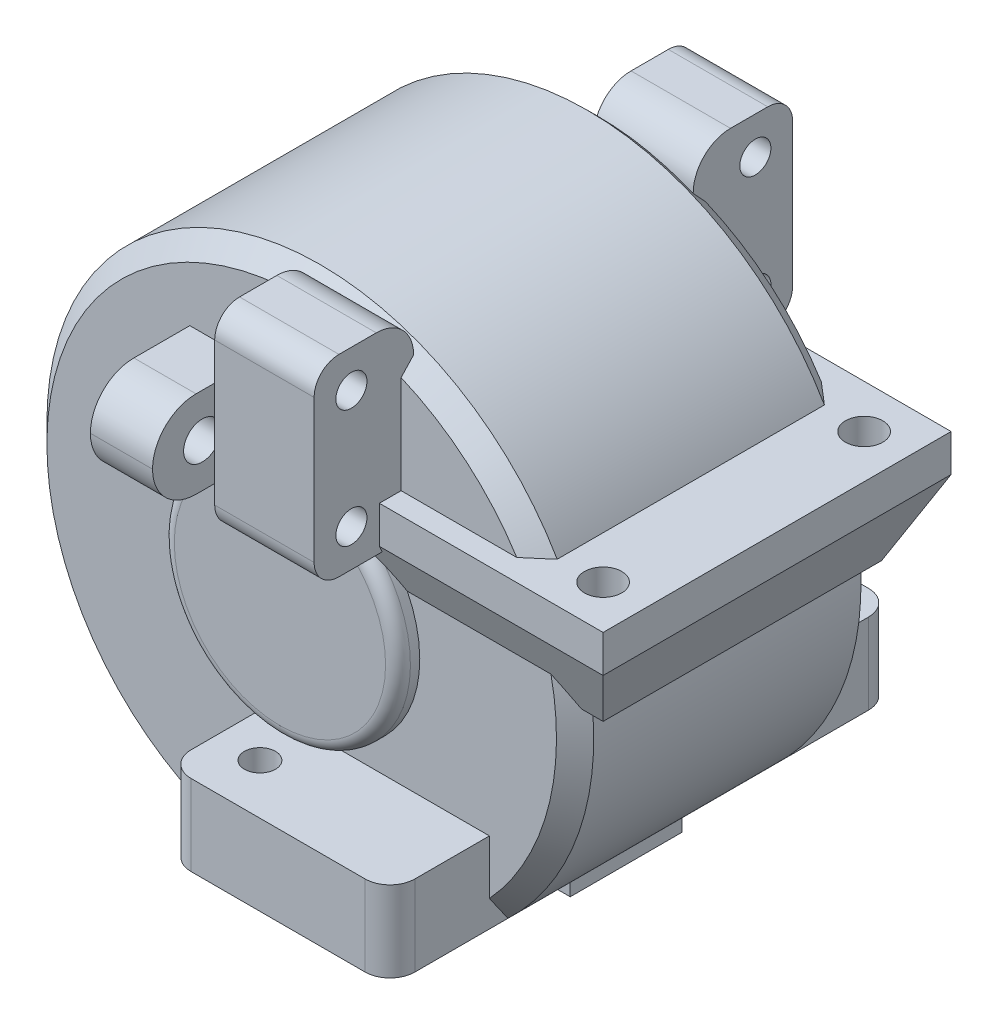
SolidWorks part; units mm, degrees
ref_plane "Front Plane" through (0, 0, 0) normal (0, 0, 1) x (1, 0, 0)
ref_plane "Top Plane" through (0, 0, 0) normal (0, 1, 0) x (1, 0, 0)
ref_plane "Right Plane" through (0, 0, 0) normal (1, 0, 0) x (0, 0, -1)
sketch "Sketch2" plane through (0, 0, 0) normal (0, 0, 1) x (1, 0, 0)
  circle A0 centre (0, 0) radius 22
  circle A1 centre (0, 0) radius 9.5
  dimension "D1" = 44
  dimension "D2" = 19
extrude "Boss-Extrude1" add sketch "Sketch2" along normal blind 12.25 and the other way blind 12.25 contours A0
extrude "Boss-Extrude2" add sketch "Sketch2<3>" along normal blind 14 and the other way blind 14 contours A1
sketch "Sketch2<3>" plane through (0, 0, 0) normal (0, 0, 1) x (1, 0, 0) same geometry as "Sketch2"
chamfer "Chamfer1" distance 1.5 angle 45 2 edges at (22, 0, -12.25) (22, 0, 12.25)
fillet "Fillet1" radius 1 2 edges at (9.5, 0, -14) (9.5, 0, 14)
sketch "Sketch3" plane through (0, 0, -12.25) normal (0, 0, -1) x (-1, 0, 0)
  line L1 (-15.105, -9.505) -> (2.895, -9.505)
  line L2 (-15.105, -9.505) -> (-15.105, -15.995)
  line L3 (-15.105, -15.995) -> (2.895, -15.995)
  line L4 (2.895, -9.505) -> (2.895, -15.995)
  circle A0 centre (0, 0) radius 22 construction
  circle A1 centre (0, 0) radius 9.5 construction
  point P4 (0, 0)
  point P6 (0, 0)
  dimension "D3" = 9.505
  dimension "D1" = 18
  dimension "D2" = 6.49
extrude "Boss-Extrude7" add sketch "Sketch3" along normal blind 8 and the other way blind 2
sketch "Sketch4" plane through (0, -9.505, 0) normal (0, 1, 0) x (1, 0, 0)
  line L1 (-2.895, 20.25) -> (15.105, 20.25) construction
  circle A0 centre (-10.395, 16.2139) radius 1.25
  circle A1 centre (0.605, 16.2139) radius 1.25
  point P6 (6.105, 20.25)
  dimension "D1" = 2.5
  dimension "D2" = 2.5
  dimension "D3" = 11
  dimension "D4" = 5.5
extrude "Cut-Extrude1" cut sketch "Sketch4" against normal through all
fillet "Fillet2" radius 2 2 edges at (15.105, -12.75, -20.25) (-2.895, -12.75, -20.25)
ref_plane "Plane1" through (0, 1.995, 0) normal (0, 1, 0) x (1, 0, 0)
sketch "Sketch5" plane through (0, 1.995, 0) normal (0, 1, 0) x (1, 0, 0)
  line L1 (0, 14) -> (26, 14)
  line L2 (0, 14) -> (0, -14)
  line L3 (0, -14) -> (26, -14)
  line L4 (26, 14) -> (26, -14)
  point P4 (0, 0)
  dimension "D1" = 28
extrude "Boss-Extrude8" add sketch "Sketch5" along normal blind 9 contours L2 L1 L4 L3
chamfer "Chamfer2" distance 6 angle 25 3 edges at (17.1313, 1.995, 14) (26, 1.995, 0) (17.1313, 1.995, -14) first distance on face at (10.1747, 4.5108, 14) first distance on face at (26, 6.495, 0) first distance on face at (10.1747, 4.5108, -14)
sketch "Sketch6" plane through (0, 10.995, 0) normal (0, 1, 0) x (1, 0, 0)
  line L2 (26, 14) -> (26, -14) construction
  circle A0 centre (22.5, 10.5) radius 1.5
  circle A1 centre (22.5, -10.5) radius 1.5
  dimension "D1" = 10.5
  dimension "D2" = 3
  dimension "D3" = 3
  dimension "D4" = 3.5
  dimension "D5" = 3.5
  dimension "D6" = 21
extrude "Cut-Extrude2" cut sketch "Sketch6" against normal blind 6
sketch "Sketch7" plane through (0, 0, -12.25) normal (0, 0, -1) x (-1, 0, 0)
  line L0 (0, 10.995) -> (-26, 10.995) construction
  line L1 (0, 7.495) -> (-8, 7.495)
  line L2 (0, 7.495) -> (0, 22.995)
  line L3 (0, 22.995) -> (-8, 22.995)
  line L4 (-8, 7.495) -> (-8, 22.995)
  line L5 (-26, 10.995) -> (-26, 7.995) construction
  line L6 (4, 13.995) -> (9, 13.995)
  line L7 (4, 13.995) -> (4, 6.995)
  line L8 (4, 6.995) -> (9, 6.995)
  line L9 (9, 13.995) -> (9, 6.995)
  line M3 (0, 10.995) -> (0, 9.5)
  arc M6 (-20.0563, 4.2421) -> (-15.105, -13.8597) centre (0, 0) ccw
  line M7 (-17.302, 10.995) -> (0, 10.995)
  dimension "D1" = 15.5
  dimension "D2" = 8
  dimension "D3" = 12
  dimension "D4" = 7
  dimension "D5" = 5
  dimension "D6" = 35
  dimension "D7" = 9
  dimension "D8" = 18
extrude "Boss-Extrude11" add sketch "Sketch7" along normal blind 7 and the other way blind 1 contours L4 L2 M7 M6 | L4 L1 L2 M3 M7 | L4 L2 L3 M6 region at (4, 9.245, -12.25) region at (4, 16.995, -12.25)
extrude "Boss-Extrude13" add sketch "Sketch7<3>" along normal blind 8 contours L6 L9 L8 L7
sketch "Sketch7<3>" plane through (0, 0, -12.25) normal (0, 0, -1) x (-1, 0, 0) same geometry as "Sketch7"
sketch "Sketch10" plane through (8, 0, 0) normal (1, 0, 0) x (0, 0, -1)
  line L0 (19.25, 7.495) -> (19.25, 22.995) construction
  line L1 (19.25, 22.995) -> (11.25, 22.995) construction
  line L2 (19.25, 7.495) -> (13.7668, 7.495) construction
  circle A0 centre (16.25, 19.995) radius 1.25
  circle A1 centre (16.25, 10.495) radius 1.25
  point P8 (0, 0)
  point P10 (16.3117, 8.646)
  dimension "D1" = 2.5
  dimension "D2" = 2.5
  dimension "D3" = 3
  dimension "D4" = 3
  dimension "D5" = 3
  dimension "D6" = 3
extrude "Cut-Extrude3" cut sketch "Sketch10" against normal through all
sketch "Sketch11" plane through (-9, 0, 0) normal (-1, 0, 0) x (0, 0, 1)
  circle A0 centre (-16.25, 10.495) radius 1.5
extrude "Cut-Extrude4" cut sketch "Sketch11" against normal blind 8
fillet "Fillet3" radius 3.5 2 edges at (-6.5, 6.995, -20.25) (-6.5, 13.995, -20.25)
fillet "Fillet4" radius 2 2 edges at (4, 22.995, -19.25) (4, 7.495, -19.25)
fillet "Fillet6" radius 3 1 edges at (4, 22.995, -11.25)
sketch "Sketch14" plane through (-4, 0, 0) normal (1, 0, 0) x (0, 0, -1)
  line L1 (12.3893, 6.9333) -> (14.5207, 6.9333)
  line L2 (12.3893, 6.9333) -> (12.3893, 10.42)
  line L3 (12.3893, 10.42) -> (14.5207, 10.42)
  line L4 (14.5207, 6.9333) -> (14.5207, 10.42)
extrude "Cut-Extrude5" cut sketch "Sketch14" along normal blind 4
sketch "Sketch15" plane through (0, 0, 0) normal (1, 0, 0) x (0, 0, -1)
  line L0 (0, 0) -> (22.5881, 0) construction
  line L1 (-14.2312, 19.8583) -> (22.5881, 19.8583)
  line L2 (-14.2312, 19.8583) -> (-14.2312, -19.1548)
  line L3 (-14.2312, -19.1548) -> (22.5881, -19.1548)
  line L4 (22.5881, 19.8583) -> (22.5881, -19.1548)
mirror "Mirror16" about plane through (0, 0, 0) normal (0, 0, 1) of "Boss-Extrude7", "Cut-Extrude1", "Fillet2", "Cut-Extrude5", "Fillet6", "Fillet4", "Fillet3", "Cut-Extrude4", "Cut-Extrude3", "Boss-Extrude13", "Boss-Extrude11"
ref_plane "Plane2" through (0, -22, 0) normal (0, -1, 0) x (-1, 0, 0)
sketch "Sketch16" plane through (0, -22, 0) normal (0, -1, 0) x (-1, 0, 0)
  line L0 (2.895, 12.25) -> (2.895, 18.25) construction
  line L1 (2.895, 9.25) -> (-9.105, 9.25)
  line L2 (2.895, 9.25) -> (2.895, 0.25)
  line L3 (2.895, 0.25) -> (-9.105, 0.25)
  line L4 (-9.105, 9.25) -> (-9.105, 0.25)
  line L5 (-13.105, 20.25) -> (0.895, 20.25) construction
  dimension "D1" = 0
  dimension "D2" = 11
  dimension "D3" = 12
  dimension "D4" = 9
extrude "Boss-Extrude14" add sketch "Sketch16" along normal blind 1 and the other way blind 4
